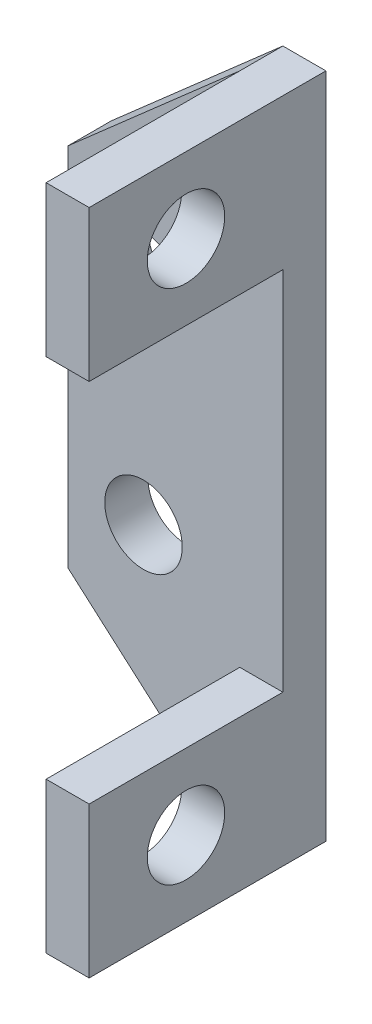
SolidWorks part; units mm, degrees
ref_plane "Front Plane" through (0, 0, 0) normal (0, 0, 1) x (1, 0, 0)
ref_plane "Top Plane" through (0, 0, 0) normal (0, 1, 0) x (1, 0, 0)
ref_plane "Right Plane" through (0, 0, 0) normal (1, 0, 0) x (0, 0, -1)
sketch "Sketch2" plane through (0, 0, 0) normal (0, 0, 1) x (1, 0, 0)
  line L1 (-9.9744, 7) -> (0, 7)
  line L2 (-9.9744, 7) -> (-9.9744, 24)
  line L3 (-9.9744, 24) -> (0, 24)
  line L4 (0, 7) -> (0, 24)
  line L6 (-6.4744, 10.5) -> (-9.9744, 10.5) construction
  line L7 (-6.4744, 10.5) -> (-6.4744, 7) construction
  line L8 (-9.9744, 15.5) -> (0, 15.5) construction
  line L9 (-6.4744, 10.5) -> (-6.4744, 20.5) construction
  line L10 (0, 7) -> (0, 0)
  line L11 (0, 0) -> (-2, 0)
  line L12 (-2, 0) -> (-9.9744, 7)
  line L13 (0, 24) -> (0, 31)
  line L14 (0, 31) -> (-2, 31)
  line L15 (-2, 31) -> (-9.9744, 24)
  circle A1 centre (-6.4744, 10.5) radius 1.4 construction
  point P15 (-6.4744, 15.5)
  dimension "D6" = 2.8
  dimension "D2" = 7
  dimension "D3" = 2
  dimension "D1" = 9.9744
  dimension "D4" = 17
  dimension "D5" = 5
extrude "Boss-Extrude1" add sketch "Sketch2" along normal blind 2 contours L12 L11 L10 L1 | L14 L15 L3 L13 | L1 L4 L3 L2 region at (-4.9872, 15.5, 0) region at (-3.4362, 4.2769, 0) region at (-3.4362, 26.7231, 0)
sketch "Sketch9" plane through (0, 0, 2) normal (0, 0, 1) x (1, 0, 0)
  line L0 (-9.9744, 15.5) -> (0, 15.5) construction
  line L1 (-9.9744, 7) -> (-9.9744, 24) construction
  point P7 (-6.4744, 10.5)
  point P18 (-6.4744, 20.5)
hole_wizard "M3 Clearance Hole1" positions "Sketch9" profile "Sketch4" hole size "M3" standard "ANSI Metric" end condition through all
sketch "Sketch4" plane through (-6.4744, 10.5, 2) normal (1, 0, 0) x (0, -1, 0)
  line L0 (0, 0) -> (0, 2)
  line L1 (0, 2) -> (1.8, 2)
  line L2 (1.8, 2) -> (1.8, 0)
  line L5 (1.8, 0) -> (0, 0)
  line L11 (0, -6.35) -> (0, 107.95) construction
  dimension "Thru Hole Dia." = 3.6
  dimension "Thru Hole Depth" = 2
sketch "Sketch6" plane through (0, 0, 2) normal (0, 0, 1) x (1, 0, 0)
  line L0 (-9.9744, 15.5) -> (0, 15.5) construction
  line L1 (0, 24) -> (-2, 24)
  line L2 (0, 24) -> (0, 31)
  line L3 (0, 31) -> (-2, 31)
  line L4 (-2, 24) -> (-2, 31)
  line L7 (0, 0) -> (-2, 0)
  line L8 (-2, 7) -> (-2, 0)
  line L9 (0, 7) -> (-2, 7)
  line L10 (0, 7) -> (0, 0)
  line L12 (0, 31) -> (0, 0) construction
  line L13 (-9.9744, 7) -> (-9.9744, 24) construction
  line L14 (0, 31) -> (-2, 31) construction
  dimension "D1" = 7
  dimension "D2" = 2
extrude "Boss-Extrude2" add sketch "Sketch6" along normal blind 9
sketch "Sketch10" plane through (-2, 0, 0) normal (-1, 0, 0) x (0, 0, 1)
  line L0 (11, 27.5) -> (2, 27.5) construction
  line L1 (11, 31) -> (11, 24) construction
  line L2 (2, 31) -> (2, 24) construction
  line L4 (11, 3.5) -> (2, 3.5) construction
  line L5 (11, 7) -> (11, 0) construction
  line L6 (2, 7) -> (2, 0) construction
  point P0 (6.5, 3.5)
  point P2 (6.5, 27.5)
  point P3 (6.5, 3.5)
  point P24 (6.5, 3.5)
hole_wizard "M3 Clearance Hole2" positions "Sketch10" profile "Sketch8" hole size "M3" standard "ANSI Metric" end condition through all
sketch "Sketch8" plane through (-2, 3.5, 6.5) normal (0, 1, 0) x (0, 0, 1)
  line L0 (0, 0) -> (0, 2)
  line L1 (0, 2) -> (1.8, 2)
  line L2 (1.8, 2) -> (1.8, 0)
  line L5 (1.8, 0) -> (0, 0)
  line L11 (0, -6.35) -> (0, 107.95) construction
  dimension "Thru Hole Dia." = 3.6
  dimension "Thru Hole Depth" = 2
equation "\"width\"= 7.30441 + 2.67"
equation "\"D1@Sketch2\"=\"width\""
